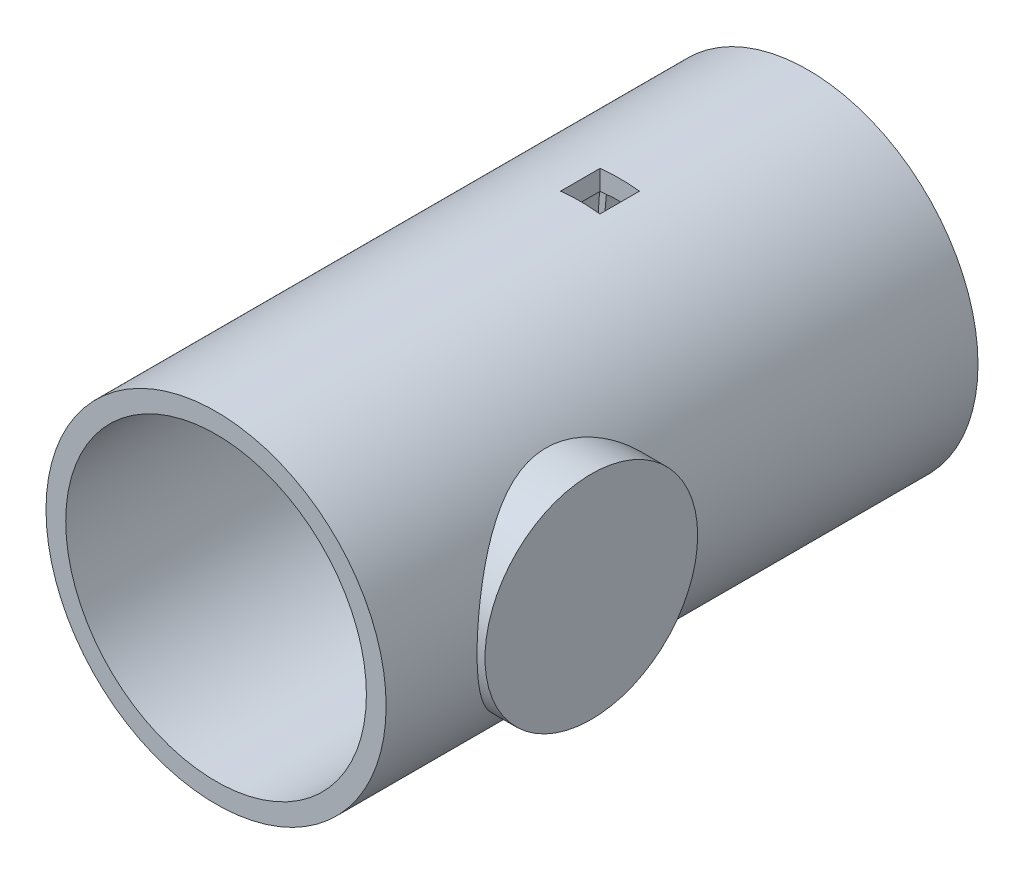
SolidWorks part; units mm, degrees
ref_plane "Front Plane" through (0, 0, 0) normal (0, 0, 1) x (1, 0, 0)
ref_plane "Top Plane" through (0, 0, 0) normal (0, 1, 0) x (1, 0, 0)
ref_plane "Right Plane" through (0, 0, 0) normal (1, 0, 0) x (0, 0, -1)
sketch "Sketch1" plane through (0, 0, 0) normal (0, 0, 1) x (1, 0, 0)
  circle A1 centre (0, 0) radius 43.1
  dimension "D1" = 86.2
extrude "Boss-Extrude1" add sketch "Sketch1" along normal blind 150
ref_plane "Plane1" through (0, 43.1, 0) normal (0, 1, 0) x (1, 0, 0)
sketch "Sketch6" plane through (0, 43.1, 0) normal (0, 1, 0) x (1, 0, 0)
  line L2 (-5, -57.7) -> (5, -57.7)
  line L3 (-5, -57.7) -> (-5, -47.7)
  line L4 (-5, -47.7) -> (5, -47.7)
  line L5 (5, -57.7) -> (5, -47.7)
  line L6 (-5, -57.7) -> (5, -47.7) construction
  line L7 (-5, -47.7) -> (5, -57.7) construction
  point P2 (0, -52.7)
  point P3 (0, 0)
  dimension "D2" = 10
  dimension "D1" = 52.7
  dimension "D3" = 10
extrude "Cut-Extrude3" cut sketch "Sketch6" against normal through all
ref_plane "Plane2" through (45.1, 0, 0) normal (1, 0, 0) x (0, 0, -1)
sketch "Sketch8" plane through (45.1, 0, 0) normal (1, 0, 0) x (0, 0, -1)
  circle A0 centre (-100, 0) radius 26.95
  dimension "D1" = 53.9
  dimension "D2" = 100
extrude "Boss-Extrude2" add sketch "Sketch8" against normal blind 20
mirror "Mirror1" [suppressed] about plane through (0, 0, 0) normal (1, 0, 0)
sketch "Sketch5" plane through (0, 0, 150) normal (0, 0, 1) x (1, 0, 0)
  circle A0 centre (0, 0) radius 31.75
  dimension "D1" = 63.5
sketch "Sketch2" plane through (0, 0, 150) normal (0, 0, 1) x (1, 0, 0)
  circle A0 centre (0, 0) radius 38.1
  dimension "D1" = 76.2
extrude "Cut-Extrude4" cut sketch "Sketch5" against normal through all
extrude "Cut-Extrude5" cut sketch "Sketch2" against normal blind 145
sketch "Sketch9" plane through (0, 0, 5) normal (0, 0, 1) x (1, 0, 0)
  circle A0 centre (0, 0) radius 38.1
  circle A1 centre (0, 0) radius 36.44
  dimension "D1" = 76.2
  dimension "D2" = 1.66
extrude "Boss-Extrude3" add sketch "Sketch9" along normal blind 10
